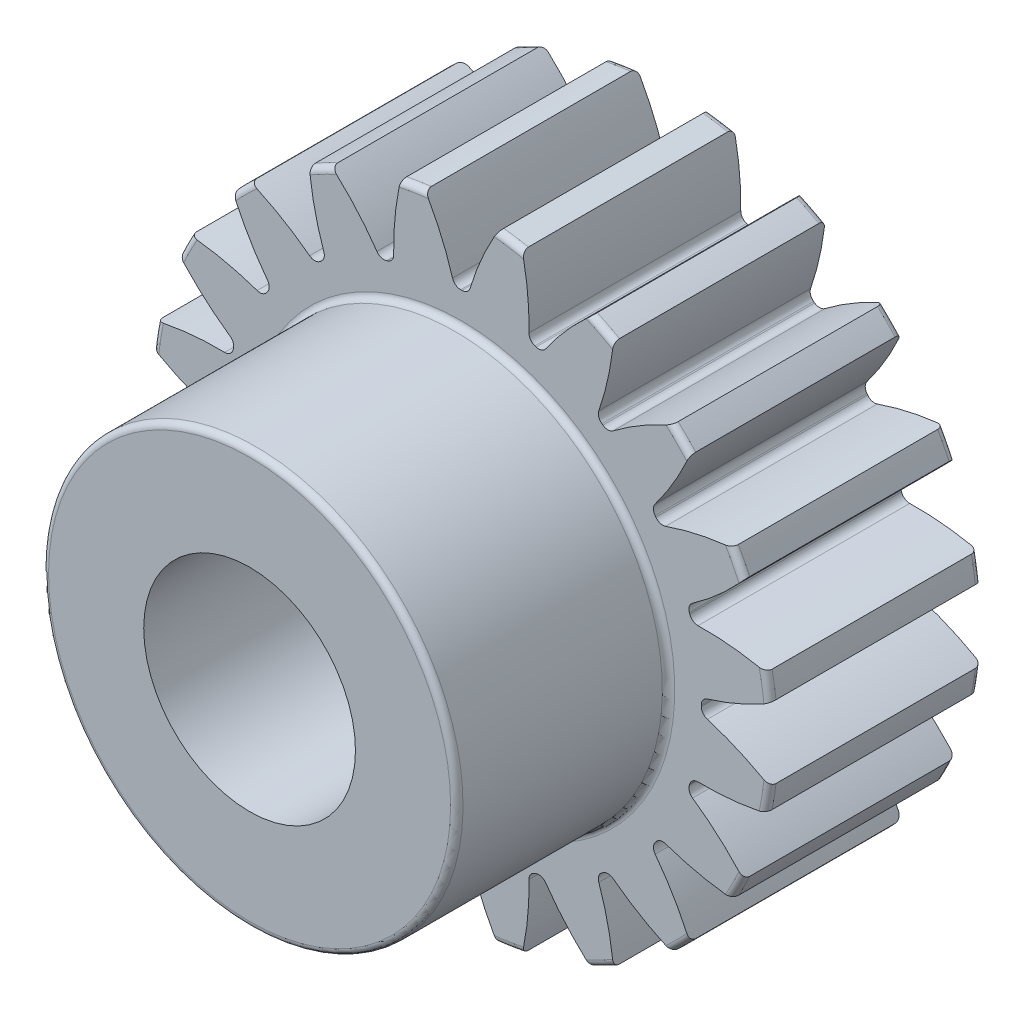
SolidWorks part; units mm, degrees
ref_plane "Front Plane" through (0, 0, 0) normal (0, 0, 1) x (1, 0, 0)
ref_plane "Top Plane" through (0, 0, 0) normal (0, 1, 0) x (1, 0, 0)
ref_plane "Right Plane" through (0, 0, 0) normal (1, 0, 0) x (0, 0, -1)
sketch "Sketch1" plane through (0, 0, 0) normal (0, 0, 1) x (1, 0, 0)
  line L0 (-254, 0) -> (254, 0) construction
  circle A0 centre (0, 0) radius 13.97 construction
  circle A1 centre (0, 0) radius 12.7 construction
  circle A2 centre (0, 0) radius 10.795 construction
  circle A3 centre (0, 0) radius 9.3218 construction
  circle A4 centre (0, 0) radius 4.7625 construction
  dimension "D2" = 1.27
  dimension "D3" = 3.175
  dimension "D1" = 3.175
sketch "Sketch2" plane through (0, 0, 0) normal (1, 0, 0) x (0, 0, -1)
  line L0 (0, 0) -> (-9.525, 0) construction
  line L1 (-9.525, 0) -> (-19.05, 0) construction
  dimension "Overall Width" = 19.05
  dimension "Face Width" = 9.525
sketch "Sketch4" plane through (0, 0, 0) normal (1, 0, 0) x (0, 0, -1)
  line L0 (-19.05, 4.7625) -> (-19.05, 9.3218)
  line L1 (-19.05, 9.3218) -> (-9.525, 9.3218)
  line L2 (-9.525, 9.3218) -> (-9.525, 13.97)
  line L3 (-9.525, 13.97) -> (0, 13.97)
  line L4 (0, 13.97) -> (0, 4.7625)
  line L5 (-9.525, 9.3218) -> (-9.525, 0) construction
  line L6 (0, 13.97) -> (0, -13.97) construction
  line L7 (-9.525, 9.3218) -> (0, 9.3218) construction
  line L12 (-19.05, 4.7625) -> (0, 4.7625)
revolve "Revolve1" add sketch "Sketch4" angle 360 about L1
fillet "Fillet2" radius 0.2794 4 edges at (0, 9.3218, 19.05) (0, 9.3218, 9.525) (0, 13.97, 9.525) (0, 13.97, 0)
sketch "Sketch7" plane through (0, 0, 9.525) normal (0, 0, 1) x (1, 0, 0)
  line L0 (0, 0) -> (0, 13.97) construction
  line L1 (0.9964, 12.6609) -> (1.5536, 13.8833) construction
  line L3 (2.1854, 13.798) -> (1.9867, 12.5436) construction
  line L4 (1.9867, 12.5436) -> (1.6887, 10.6621) construction
  line L5 (0, 0) -> (1.6887, 10.6621) construction
  line L6 (0.9964, 12.6609) -> (0, 0) construction
  line L7 (0.9964, 12.6609) -> (1.0961, 13.9269) construction
  line L8 (0.9964, 12.6609) -> (0, 0) construction
  circle A0 centre (0, 0) radius 13.97 construction
  arc A1 (-0.0294, 10.795) -> (0.0294, 10.795) centre (0, 0) cw
  circle A2 centre (0, 0) radius 10.795 construction
  arc A3 (-0.9964, 12.6609) -> (0.9964, 12.6609) centre (0, 0) cw construction
  circle A4 centre (0, 0) radius 12.7 construction
  arc A5 (2.7366, 13.6993) -> (1.6307, 13.8745) centre (0, 0) ccw construction
  arc A6 (0.9964, 12.6609) -> (2.9648, 12.3491) centre (0, 0) cw construction
  arc A7 (-1.6307, 13.8745) -> (1.6307, 13.8745) centre (0, 0) cw
  arc A8 (0.3952, 11.0658) -> (1.6307, 13.8745) centre (12.5529, 7.3942) cw
  arc A9 (-0.3952, 11.0658) -> (-1.6307, 13.8745) centre (-12.5529, 7.3942) ccw
  arc A10 (-0.0294, 10.795) -> (-0.3952, 11.0658) centre (-0.0305, 11.176) cw
  arc A11 (0.0294, 10.795) -> (0.3952, 11.0658) centre (0.0305, 11.176) ccw
  point P26 (-0.3154, 10.7904)
  point P29 (0.3154, 10.7904)
  dimension "D4" = 0.381
  dimension "D5" = 12.7
  dimension "D3" = 20
  dimension "D1" = 3.9898
  dimension "D2" = 1.9949
extrude "Cut-Extrude2" cut sketch "Sketch7" against normal through all
pattern_circular "CirPattern1" count 20 over 360 about axis through (0, 0, 19.05) along (0, 0, -1) of "Cut-Extrude2"
equation "\"D1@Sketch1\"=2.5*(\"Pitch Dia.@Sketch1\"/\"Number of Teeth@Sketch1\")"
equation "\"D1@CirPattern1\"=\"Number of Teeth@Sketch1\""
equation "\"D1@Fillet2\"=\"OD@Sketch1\"*.01"
equation "\"D1@Sketch7\"=3.14159*(\"Pitch Dia.@Sketch1\"/\"Number of Teeth@Sketch1\")"
equation "\"D2@Sketch7\"=\"D1@Sketch7\"/2"
equation "\"D4@Sketch7\"=\"D1@Sketch7\"*.0955"
equation "\"D5@Sketch7\"=\"Pitch Dia.@Sketch1\"/2"
